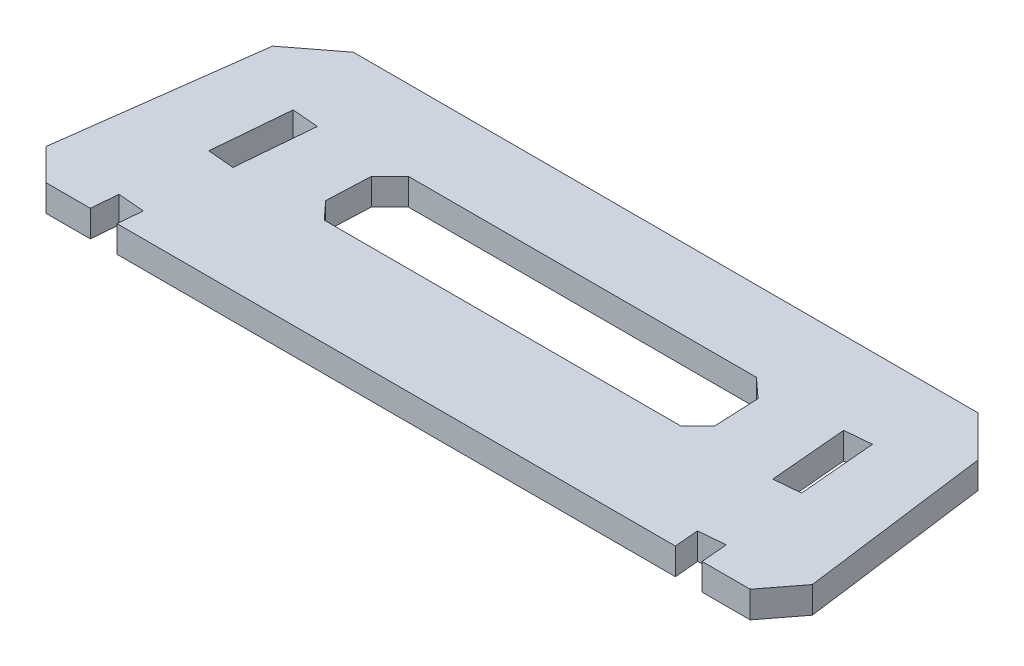
SolidWorks part; units mm, degrees
note: '?' marks a value the reader was unsure of.
ref_plane "Front Plane" through (0, 0, 0) normal (0, 0, 1) x (1, 0, 0)
ref_plane "Top Plane" through (0, 0, 0) normal (0, 1, 0) x (1, 0, 0)
ref_plane "Right Plane" through (0, 0, 0) normal (1, 0, 0) x (0, 0, -1)
ref_axis "Axis3" through (146.5957, 0, -62.9662) along (0.0868, 0, 0.9962)?
ref_axis "Axis4" through (-153.8517, 0, 20.2865) along (0.0868, 0, -0.9962)?
sketch "Sketch2" plane through (0, 0, 0) normal (0, 1, 0) x (1, 0, 0)
  line L0 (0, 0) -> (0, -150.573) construction
  line L1 (-225, 0) -> (225, 0) construction
  line L2 (-225, 0) -> (-225, -150.573) construction
  line L3 (-225, -150.573) -> (225, -150.573) construction
  line L4 (225, 0) -> (225, -150.573) construction
  line L5 (197.9803, 0) -> (217.753, -150.573)
  line L6 (217.753, -150.573) -> (-217.753, -150.573) construction
  line L7 (-217.753, -150.573) -> (-197.9803, 0)
  line L8 (-197.9803, 0) -> (197.9803, 0)
  line L10 (152.0836, 0) -> (165.2069, -150.573) construction
  line L12 (146.5957, 62.9662) -> (168.3024, -186.0897) construction
  line L13 (-152.0836, 0) -> (-165.2069, -150.573) construction
  line L15 (108.4922, -45.1719) -> (110.4495, -90.3438)
  line L16 (110.4495, -90.3438) -> (-110.4495, -90.3438)
  line L17 (-110.4495, -90.3438) -> (-108.4922, -45.1719)
  line L18 (-108.4922, -45.1719) -> (108.4922, -45.1719)
  line L19 (-225, -90.3438) -> (225, -90.3438) construction
  line L20 (-225, -45.1719) -> (225, -45.1719) construction
  line L21 (-163.549, -45.1719) -> (-167.3725, -89.0414)
  line L22 (-167.3725, -89.0414) -> (-152.4292, -90.3438)
  line L23 (-152.4292, -90.3438) -> (-148.6057, -46.4743)
  line L24 (-148.6057, -46.4743) -> (-163.549, -45.1719)
  line L25 (152.4292, -90.3438) -> (148.6057, -46.4743)
  line L26 (167.3725, -89.0414) -> (152.4292, -90.3438)
  line L27 (163.549, -45.1719) -> (167.3725, -89.0414)
  line L28 (148.6057, -46.4743) -> (163.549, -45.1719)
  line L29 (108.4922, -45.1719) -> (148.4922, -45.1719) construction
  line L30 (172.7353, -150.573) -> (171.4329, -135.6296)
  line L31 (171.4329, -135.6296) -> (156.4896, -136.932)
  line L32 (156.4896, -136.932) -> (157.6785, -150.573)
  line L33 (-172.7353, -150.573) -> (-171.4329, -135.6296)
  line L34 (-171.4329, -135.6296) -> (-156.4896, -136.932)
  line L35 (-156.4896, -136.932) -> (-157.6785, -150.573)
  line L36 (217.753, -150.573) -> (172.7353, -150.573)
  line L37 (157.6785, -150.573) -> (-157.6785, -150.573)
  line L38 (-217.753, -150.573) -> (-172.7353, -150.573)
  dimension "D1" = 5
  dimension "D2" = 15
  dimension "D3" = 40
extrude "Boss-Extrude1" add sketch "Sketch2" against normal up to vertex (15 mm away)
chamfer "Chamfer1" distance 10 angle 45 4 edges at (-108.4922, -7.5, 45.1719) (108.4922, -7.5, 45.1719) (110.4495, -7.5, 90.3438) (-110.4495, -7.5, 90.3438)
chamfer "Chamfer2" distance 20 angle 45 4 edges at (217.753, -7.5, 150.573) (-217.753, -7.5, 150.573) (-197.9803, -7.5, 0) (197.9803, -7.5, 0)
